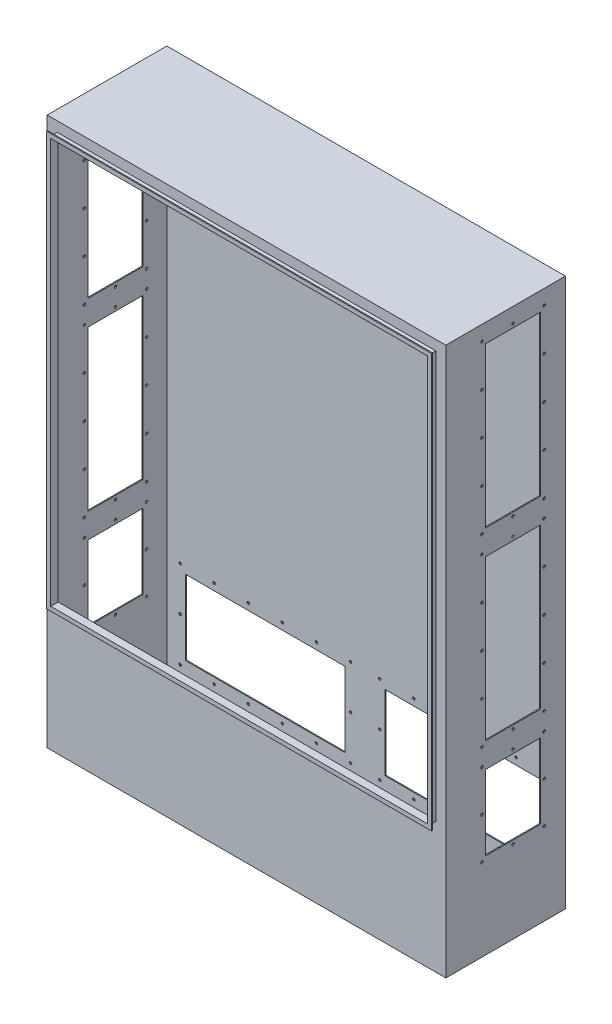
SolidWorks part; units mm, degrees
ref_plane "Front Plane" through (0, 0, 0) normal (0, 0, 1) x (1, 0, 0)
ref_plane "Top Plane" through (0, 0, 0) normal (0, 1, 0) x (1, 0, 0)
ref_plane "Right Plane" through (0, 0, 0) normal (1, 0, 0) x (0, 0, -1)
sketch "Sketch1" plane through (0, 0, 0) normal (0, 0, 1) x (1, 0, 0)
  line L1 (-508, -698.5) -> (508, -698.5)
  line L2 (-508, -698.5) -> (-508, 698.5)
  line L3 (-508, 698.5) -> (508, 698.5)
  line L4 (508, -698.5) -> (508, 698.5)
  line L5 (-508, -698.5) -> (508, 698.5) construction
  line L6 (-508, 698.5) -> (508, -698.5) construction
  point P0 (0, 0)
  dimension "D1" = 1397
  dimension "D2" = 1016
extrude "Main Panel" add sketch "Sketch1" along normal blind 2.54
sketch "Sketch2" plane through (0, 0, 2.54) normal (0, 0, 1) x (1, 0, 0)
  line L10 (-508, -698.5) -> (508, -698.5) construction
  line L11 (508, -698.5) -> (508, 698.5) construction
  line L12 (508, 698.5) -> (-508, 698.5) construction
  line L13 (-508, 698.5) -> (-508, -698.5) construction
  line L14 (-505.46, -695.96) -> (505.46, -695.96)
  line L15 (505.46, -695.96) -> (505.46, 695.96)
  line L16 (505.46, 695.96) -> (-505.46, 695.96)
  line L17 (-505.46, 695.96) -> (-505.46, -695.96)
  line L18 (-505.46, -695.96) -> (505.46, -695.96)
  line L19 (505.46, -695.96) -> (505.46, 695.96)
  line L20 (505.46, 695.96) -> (-505.46, 695.96)
  line L21 (-505.46, 695.96) -> (-505.46, -695.96)
  line L22 (-508, -698.5) -> (508, -698.5)
  line L23 (508, -698.5) -> (508, 698.5)
  line L24 (508, 698.5) -> (-508, 698.5)
  line L25 (-508, 698.5) -> (-508, -698.5)
  dimension "D1" = 2.54
extrude "Walls" add sketch "Sketch2" along normal blind 302.26
sketch "Sketch3" plane through (508, 0, 0) normal (1, 0, 0) x (0, 0, -1)
  line L0 (0, 698.5) -> (0, -698.5) construction
  line L1 (-203.2, 650.875) -> (-63.5, 650.875)
  line L2 (-203.2, 650.875) -> (-203.2, 244.475)
  line L3 (-203.2, 244.475) -> (-63.5, 244.475)
  line L4 (-63.5, 650.875) -> (-63.5, 244.475)
  line L5 (-203.2, 180.975) -> (-63.5, 180.975)
  line L6 (-203.2, 180.975) -> (-203.2, -225.425)
  line L7 (-203.2, -225.425) -> (-63.5, -225.425)
  line L8 (-63.5, 180.975) -> (-63.5, -225.425)
  line L9 (-203.2, -288.925) -> (-63.5, -288.925)
  line L10 (-203.2, -288.925) -> (-203.2, -479.425)
  line L11 (-203.2, -479.425) -> (-63.5, -479.425)
  line L12 (-63.5, -288.925) -> (-63.5, -479.425)
  line L14 (-304.8, 698.5) -> (0, 698.5) construction
  dimension "D1" = 139.7
  dimension "D2" = 406.4
  dimension "D3" = 190.5
  dimension "D4" = 63.5
  dimension "D5" = 47.625
  dimension "D6" = 63.5
  dimension "D7" = 63.5
extrude "Side Cuts" cut sketch "Sketch3" against normal through all both and the other way through all
sketch "Sketch4" plane through (0, 0, 0) normal (0, 0, -1) x (-1, 0, 0)
  line L12 (-51.2, -441.325) -> (-457.6, -441.325)
  line L13 (-457.6, -441.325) -> (-457.6, -631.825)
  line L14 (-457.6, -631.825) -> (-51.2, -631.825)
  line L16 (-51.2, -631.825) -> (-51.2, -441.325)
  line L55 (-51.2, -441.325) -> (-457.6, -441.325)
  line L56 (-457.6, -441.325) -> (-457.6, -631.825)
  line L57 (-457.6, -631.825) -> (-51.2, -631.825)
  line L58 (-51.2, -631.825) -> (-51.2, -441.325)
  circle A1 centre (-37.23, -536.0786) radius 3.175
  circle A3 centre (-37.23, -536.0786) radius 3.175
  circle A5 centre (-471.57, -536.0786) radius 3.175
  circle A7 centre (-471.57, -536.0786) radius 3.175
  circle A9 centre (-471.57, -647.725) radius 3.175
  circle A11 centre (-471.57, -647.725) radius 3.175
  circle A13 centre (-37.23, -647.725) radius 3.175
  circle A15 centre (-37.23, -647.725) radius 3.175
  circle A17 centre (-37.23, -424.4322) radius 3.175
  circle A19 centre (-37.23, -424.4322) radius 3.175
  circle A21 centre (-471.57, -424.4322) radius 3.175
  circle A23 centre (-471.57, -424.4322) radius 3.175
  circle A25 centre (-124.098, -424.4322) radius 3.175
  circle A27 centre (-124.098, -424.4322) radius 3.175
  circle A29 centre (-210.966, -424.4322) radius 3.175
  circle A31 centre (-210.966, -424.4322) radius 3.175
  circle A33 centre (-297.834, -424.4322) radius 3.175
  circle A35 centre (-297.834, -424.4322) radius 3.175
  circle A37 centre (-384.702, -424.4322) radius 3.175
  circle A39 centre (-384.702, -424.4322) radius 3.175
  circle A41 centre (-384.702, -647.725) radius 3.175
  circle A43 centre (-384.702, -647.725) radius 3.175
  circle A45 centre (-297.834, -647.725) radius 3.175
  circle A47 centre (-297.834, -647.725) radius 3.175
  circle A49 centre (-210.966, -647.725) radius 3.175
  circle A51 centre (-210.966, -647.725) radius 3.175
  circle A53 centre (-124.098, -647.725) radius 3.175
  circle A55 centre (-124.098, -647.725) radius 3.175
  dimension "D1" = 0
  dimension "D2" = 0
  dimension "D3" = 0
  dimension "D4" = 0
  dimension "D5" = 0
  dimension "D6" = 0
  dimension "D7" = 0
  dimension "D8" = 0
  dimension "D9" = 0
  dimension "D10" = 0
  dimension "D11" = 0
  dimension "D12" = 0
  dimension "D13" = 0
  dimension "D14" = 0
  dimension "D15" = 0
extrude "Cam Holes" cut sketch "Sketch4" against normal up to next contours L57 L58 L55 L56 | A35 | A51 | A47 | A43 | A39 | A31 | A27 | A55 | A23 | A19 | A7 | A11 | A15 | A3 region at (254.4, -536.575, 0)
sketch "Sketch5" plane through (0, -695.96, 0) normal (0, 1, 0) x (1, 0, 0)
  line L1 (-304.8, -117.475) -> (304.8, -117.475)
  line L2 (-304.8, -117.475) -> (-304.8, -219.075)
  line L3 (-304.8, -219.075) -> (304.8, -219.075)
  line L4 (304.8, -117.475) -> (304.8, -219.075)
  line L5 (-505.46, -304.8) -> (505.46, -304.8) construction
  point P6 (0, -304.8)
  point P7 (0, -219.075)
  dimension "D1" = 85.725
  dimension "D2" = 609.6
  dimension "D3" = 101.6
extrude "Bottom Trap Door" cut sketch "Sketch5" against normal up to next
sketch "Sketch6" plane through (0, 0, 304.8) normal (0, 0, 1) x (1, 0, 0)
  line L0 (-508, -698.5) -> (508, -698.5) construction
  line L1 (508, -698.5) -> (508, 698.5) construction
  line L2 (-508, 698.5) -> (-508, -698.5) construction
  line L3 (508, 698.5) -> (-508, 698.5) construction
  line L4 (-508, -698.5) -> (508, -698.5)
  line L5 (508, -698.5) -> (508, 698.5)
  line L6 (-508, 698.5) -> (-508, -698.5)
  line L7 (508, 698.5) -> (-508, 698.5)
  line L9 (-482.6, 673.1) -> (482.6, 673.1)
  line L10 (-482.6, 673.1) -> (-482.6, -365.125)
  line L11 (-482.6, -365.125) -> (482.6, -365.125)
  line L12 (482.6, 673.1) -> (482.6, -365.125)
  point P8 (0, -365.125)
  dimension "D1" = 333.375
  dimension "D2" = 25.4
  dimension "D3" = 25.4
extrude "Front Face" add sketch "Sketch6" against normal blind 2.54
sketch "Sketch7" plane through (0, 0, 304.8) normal (0, 0, 1) x (1, 0, 0)
  line L0 (482.6, -365.125) -> (482.6, 673.1) construction
  line L1 (-482.6, -365.125) -> (482.6, -365.125) construction
  line L2 (-482.6, 673.1) -> (-482.6, -365.125) construction
  line L3 (482.6, 673.1) -> (-482.6, 673.1) construction
  line L4 (482.6, -365.125) -> (482.6, 673.1)
  line L5 (-482.6, -365.125) -> (482.6, -365.125)
  line L6 (-482.6, 673.1) -> (-482.6, -365.125)
  line L7 (482.6, 673.1) -> (-482.6, 673.1)
  line L8 (480.06, 670.56) -> (-480.06, 670.56)
  line L9 (-480.06, 670.56) -> (-480.06, -362.585)
  line L10 (-480.06, -362.585) -> (480.06, -362.585)
  line L11 (480.06, -362.585) -> (480.06, 670.56)
  dimension "D1" = 2.54
extrude "Boss-Extrude1" add sketch "Sketch7" along normal blind 19.05 separate body
sketch "Sketch8" plane through (0, 0, 323.85) normal (0, 0, 1) x (1, 0, 0)
  line L0 (-482.6, -365.125) -> (482.6, -365.125) construction
  line L1 (482.6, -365.125) -> (482.6, 673.1) construction
  line L2 (-482.6, 673.1) -> (-482.6, -365.125) construction
  line L3 (482.6, 673.1) -> (-482.6, 673.1) construction
  line L4 (-482.6, -365.125) -> (482.6, -365.125)
  line L5 (482.6, -365.125) -> (482.6, 673.1)
  line L6 (-482.6, 673.1) -> (-482.6, -365.125)
  line L7 (482.6, 673.1) -> (-482.6, 673.1)
  line L8 (490.6, 681.1) -> (-490.6, 681.1)
  line L9 (-490.6, 681.1) -> (-490.6, -373.125)
  line L10 (-490.6, -373.125) -> (490.6, -373.125)
  line L11 (490.6, -373.125) -> (490.6, 681.1)
  dimension "D1" = 8
extrude "Boss-Extrude2" add sketch "Sketch8" against normal blind 2.54
sketch3d "3DSketch1"
  circle A1 centre (508, 190.5, 133.35) radius 3.175
  circle A2 centre (508, 190.5, 133.35) radius 3.175
  circle A3 centre (508, 341.3125, 53.975) radius 3.175
  circle A4 centre (508, 341.3125, 53.975) radius 3.175
  circle A5 centre (508, 447.675, 53.975) radius 3.175
  circle A6 centre (508, 447.675, 53.975) radius 3.175
  circle A7 centre (508, 554.0375, 53.975) radius 3.175
  circle A8 centre (508, 554.0375, 53.975) radius 3.175
  circle A9 centre (508, 660.4, 53.975) radius 3.175
  circle A10 centre (508, 660.4, 53.975) radius 3.175
  circle A11 centre (508, 660.4, 212.725) radius 3.175
  circle A12 centre (508, 660.4, 212.725) radius 3.175
  circle A13 centre (508, 660.4, 133.35) radius 3.175
  circle A14 centre (508, 660.4, 133.35) radius 3.175
  circle A15 centre (508, 190.5, 53.975) radius 3.175
  circle A16 centre (508, 190.5, 53.975) radius 3.175
  circle A17 centre (508, 84.1375, 53.975) radius 3.175
  circle A18 centre (508, 84.1375, 53.975) radius 3.175
  circle A19 centre (508, 190.5, 212.725) radius 3.175
  circle A20 centre (508, 190.5, 212.725) radius 3.175
  circle A21 centre (508, 341.3125, 212.725) radius 3.175
  circle A22 centre (508, 341.3125, 212.725) radius 3.175
  circle A23 centre (508, 234.95, 212.725) radius 3.175
  circle A24 centre (508, 234.95, 212.725) radius 3.175
  circle A25 centre (508, 234.95, 133.35) radius 3.175
  circle A26 centre (508, 234.95, 133.35) radius 3.175
  circle A27 centre (508, 234.95, 53.975) radius 3.175
  circle A28 centre (508, 234.95, 53.975) radius 3.175
  circle A29 centre (508, -128.5875, 53.975) radius 3.175
  circle A30 centre (508, -128.5875, 53.975) radius 3.175
  circle A31 centre (508, -22.225, 53.975) radius 3.175
  circle A32 centre (508, -22.225, 53.975) radius 3.175
  circle A33 centre (508, 554.0375, 212.725) radius 3.175
  circle A34 centre (508, 554.0375, 212.725) radius 3.175
  circle A35 centre (508, 447.675, 212.725) radius 3.175
  circle A36 centre (508, 447.675, 212.725) radius 3.175
  circle A37 centre (508, -234.95, 212.725) radius 3.175
  circle A38 centre (508, -234.95, 212.725) radius 3.175
  circle A39 centre (508, -128.5875, 212.725) radius 3.175
  circle A40 centre (508, -128.5875, 212.725) radius 3.175
  circle A41 centre (508, -234.95, 53.975) radius 3.175
  circle A42 centre (508, -234.95, 53.975) radius 3.175
  circle A43 centre (508, -22.225, 212.725) radius 3.175
  circle A44 centre (508, -22.225, 212.725) radius 3.175
  circle A45 centre (508, -234.95, 133.35) radius 3.175
  circle A46 centre (508, -234.95, 133.35) radius 3.175
  circle A47 centre (508, 84.1375, 212.725) radius 3.175
  circle A48 centre (508, 84.1375, 212.725) radius 3.175
  circle A49 centre (508, -384.175, 53.975) radius 3.175
  circle A50 centre (508, -384.175, 53.975) radius 3.175
  circle A51 centre (508, -384.175, 212.725) radius 3.175
  circle A52 centre (508, -384.175, 212.725) radius 3.175
  circle A53 centre (508, -279.4, 212.725) radius 3.175
  circle A54 centre (508, -279.4, 212.725) radius 3.175
  circle A55 centre (508, -279.4, 53.975) radius 3.175
  circle A56 centre (508, -279.4, 53.975) radius 3.175
  circle A57 centre (508, -488.95, 133.35) radius 3.175
  circle A58 centre (508, -488.95, 133.35) radius 3.175
  circle A59 centre (508, -279.4, 133.35) radius 3.175
  circle A60 centre (508, -279.4, 133.35) radius 3.175
  circle A61 centre (508, -488.95, 212.725) radius 3.175
  circle A62 centre (508, -488.95, 212.725) radius 3.175
  circle A63 centre (508, -488.95, 53.975) radius 3.175
  circle A64 centre (508, -488.95, 53.975) radius 3.175
  point P9 (504.825, 190.5, 133.35)
  point P11 (504.825, 190.5, 133.35)
  point P14 (504.825, 341.3125, 53.975)
  point P16 (504.825, 341.3125, 53.975)
  point P19 (504.825, 447.675, 53.975)
  point P21 (504.825, 447.675, 53.975)
  point P24 (504.825, 554.0375, 53.975)
  point P26 (504.825, 554.0375, 53.975)
  point P29 (504.825, 660.4, 53.975)
  point P31 (504.825, 660.4, 53.975)
  point P34 (504.825, 660.4, 212.725)
  point P36 (504.825, 660.4, 212.725)
  point P39 (504.825, 660.4, 133.35)
  point P41 (504.825, 660.4, 133.35)
  point P44 (504.825, 190.5, 53.975)
  point P46 (504.825, 190.5, 53.975)
  point P49 (504.825, 84.1375, 53.975)
  point P51 (504.825, 84.1375, 53.975)
  point P54 (504.825, 190.5, 212.725)
  point P56 (504.825, 190.5, 212.725)
  point P59 (504.825, 341.3125, 212.725)
  point P61 (504.825, 341.3125, 212.725)
  point P64 (504.825, 234.95, 212.725)
  point P66 (504.825, 234.95, 212.725)
  point P69 (504.825, 234.95, 133.35)
  point P71 (504.825, 234.95, 133.35)
  point P74 (504.825, 234.95, 53.975)
  point P76 (504.825, 234.95, 53.975)
  point P79 (504.825, -128.5875, 53.975)
  point P81 (504.825, -128.5875, 53.975)
  point P84 (504.825, -22.225, 53.975)
  point P86 (504.825, -22.225, 53.975)
  point P89 (504.825, 554.0375, 212.725)
  point P91 (504.825, 554.0375, 212.725)
  point P94 (504.825, 447.675, 212.725)
  point P96 (504.825, 447.675, 212.725)
  point P99 (504.825, -234.95, 212.725)
  point P101 (504.825, -234.95, 212.725)
  point P104 (504.825, -128.5875, 212.725)
  point P106 (504.825, -128.5875, 212.725)
  point P109 (504.825, -234.95, 53.975)
  point P111 (504.825, -234.95, 53.975)
  point P114 (504.825, -22.225, 212.725)
  point P116 (504.825, -22.225, 212.725)
  point P119 (504.825, -234.95, 133.35)
  point P121 (504.825, -234.95, 133.35)
  point P124 (504.825, 84.1375, 212.725)
  point P126 (504.825, 84.1375, 212.725)
  point P129 (504.825, -384.175, 53.975)
  point P131 (504.825, -384.175, 53.975)
  point P134 (504.825, -384.175, 212.725)
  point P136 (504.825, -384.175, 212.725)
  point P139 (504.825, -279.4, 212.725)
  point P141 (504.825, -279.4, 212.725)
  point P144 (504.825, -279.4, 53.975)
  point P146 (504.825, -279.4, 53.975)
  point P149 (504.825, -488.95, 133.35)
  point P151 (504.825, -488.95, 133.35)
  point P154 (504.825, -279.4, 133.35)
  point P156 (504.825, -279.4, 133.35)
  point P159 (504.825, -488.95, 212.725)
  point P161 (504.825, -488.95, 212.725)
  point P164 (504.825, -488.95, 53.975)
  point P166 (504.825, -488.95, 53.975)
  dimension "D2" = 0
  dimension "D3" = 0
  dimension "D4" = 0
  dimension "D5" = 0
  dimension "D6" = 0
  dimension "D7" = 0
  dimension "D8" = 0
  dimension "D9" = 0
  dimension "D10" = 0
  dimension "D11" = 0
  dimension "D12" = 0
  dimension "D13" = 0
  dimension "D14" = 0
  dimension "D15" = 0
  dimension "D16" = 0
  dimension "D17" = 0
  dimension "D18" = 0
  dimension "D19" = 0
  dimension "D20" = 0
  dimension "D21" = 0
  dimension "D22" = 0
  dimension "D23" = 0
  dimension "D24" = 0
  dimension "D25" = 0
  dimension "D26" = 0
  dimension "D27" = 0
  dimension "D28" = 0
  dimension "D29" = 0
  dimension "D30" = 0
  dimension "D31" = 0
  dimension "D32" = 0
  dimension "D33" = 0
extrude "Cut-Extrude1" cut sketch "3DSketch1" along direction (-1, 0, 0) on the side of the normal through all both and the other way through all
ref_plane "CenterofPanel" through (0, 0, 0) normal (1, 0, 0) x (0, 0, -1)
mirror "Mirror1" about plane through (0, 0, 0) normal (1, 0, 0) of "Cam Holes"
